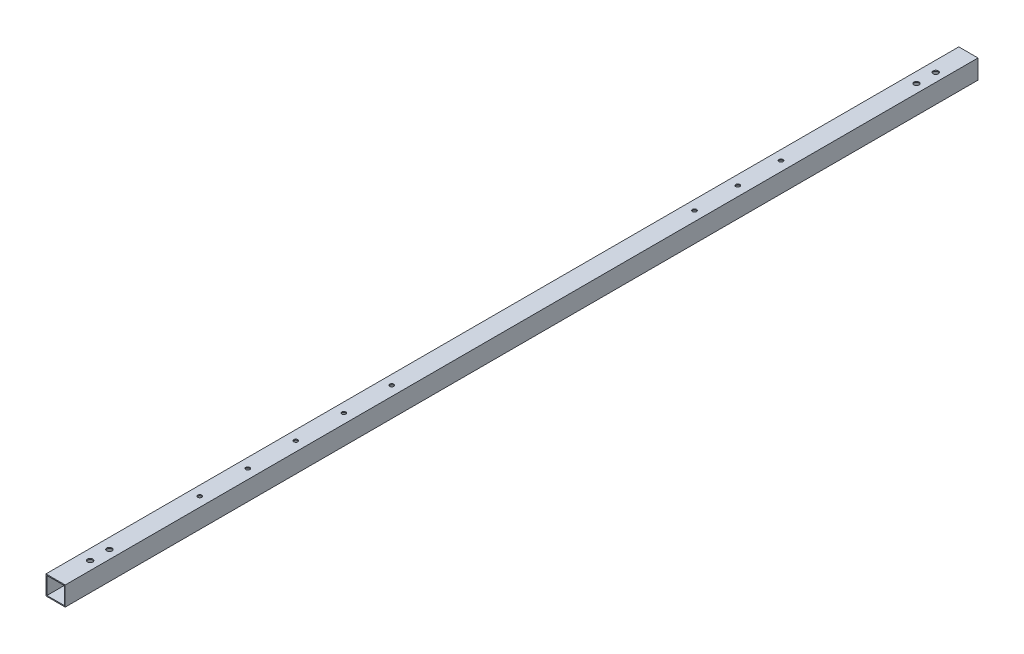
SolidWorks part; units mm, degrees
material "6061 合金"
ref_plane "前视基准面" through (0, 0, 0) normal (0, 0, 1) x (1, 0, 0)
ref_plane "上视基准面" through (0, 0, 0) normal (0, 1, 0) x (1, 0, 0)
ref_plane "右视基准面" through (0, 0, 0) normal (1, 0, 0) x (0, 0, -1)
other "Configuration Table"
sketch "草图1" plane through (0, 0, 0) normal (0, 0, 1) x (1, 0, 0)
  line L1 (0, 0) -> (20, 0)
  line L2 (0, 0) -> (0, -20)
  line L3 (0, -20) -> (20, -20)
  line L4 (20, 0) -> (20, -20)
  dimension "D1" = 20
extrude "拉伸-薄壁1" add sketch "草图1" along normal blind 950 thin thin type one direction reverse wall 1
sketch "草图2" plane through (0, 0, 0) normal (0, 1, 0) x (1, 0, 0)
  line L0 (20, -950) -> (20, 0) construction
  line L1 (20, 0) -> (0, 0) construction
  line L2 (20, -475) -> (-658.8172, -475) construction
  circle A0 centre (11, -35) radius 2.75
  circle A1 centre (11, -55) radius 2.75
  circle A2 centre (11, -895) radius 2.75
  circle A3 centre (11, -915) radius 2.75
  dimension "D1" = 5.5
  dimension "D2" = 9
  dimension "D3" = 35
  dimension "D5" = 20
  dimension "D4" = 2
extrude "切除-拉伸1" cut sketch "草图2" against normal blind 37
sketch "草图3" plane through (0, 0, 0) normal (0, 1, 0) x (1, 0, 0)
  line L0 (20, -950) -> (20, 0) construction
  circle A0 centre (10, -195) radius 2.1
  circle A1 centre (11, -55) radius 2.75 construction
  circle A2 centre (10, -240) radius 2.1
  circle A3 centre (10, -285) radius 2.1
  dimension "D1" = 4.2
  dimension "D2" = 140
  dimension "D3" = 10
  dimension "D5" = 45
  dimension "D4" = 3
extrude "切除-拉伸2" cut sketch "草图3" against normal blind 37
sketch "草图4" plane through (0, 0, 0) normal (0, 1, 0) x (1, 0, 0)
  line L0 (10, -950) -> (10, -522.0411) construction
  line L1 (20, -950) -> (0, -950) construction
  line L6 (10, -750) -> (10, -322.0411) construction
  line L7 (10, -800) -> (10, -372.0411) construction
  line L8 (10, -850) -> (10, -422.0411) construction
  line L9 (10, -900) -> (10, -472.0411) construction
  circle A0 centre (10, -800) radius 2.1
  circle A1 centre (10, -750) radius 2.1
  circle A2 centre (10, -700) radius 2.1
  circle A3 centre (10, -650) radius 2.1
  circle A4 centre (10, -600) radius 2.1
  dimension "D1" = 4.2
  dimension "D2" = 150
  dimension "D4" = 50
  dimension "D3" = 5
extrude "切除-拉伸3" cut sketch "草图4" against normal blind 37
